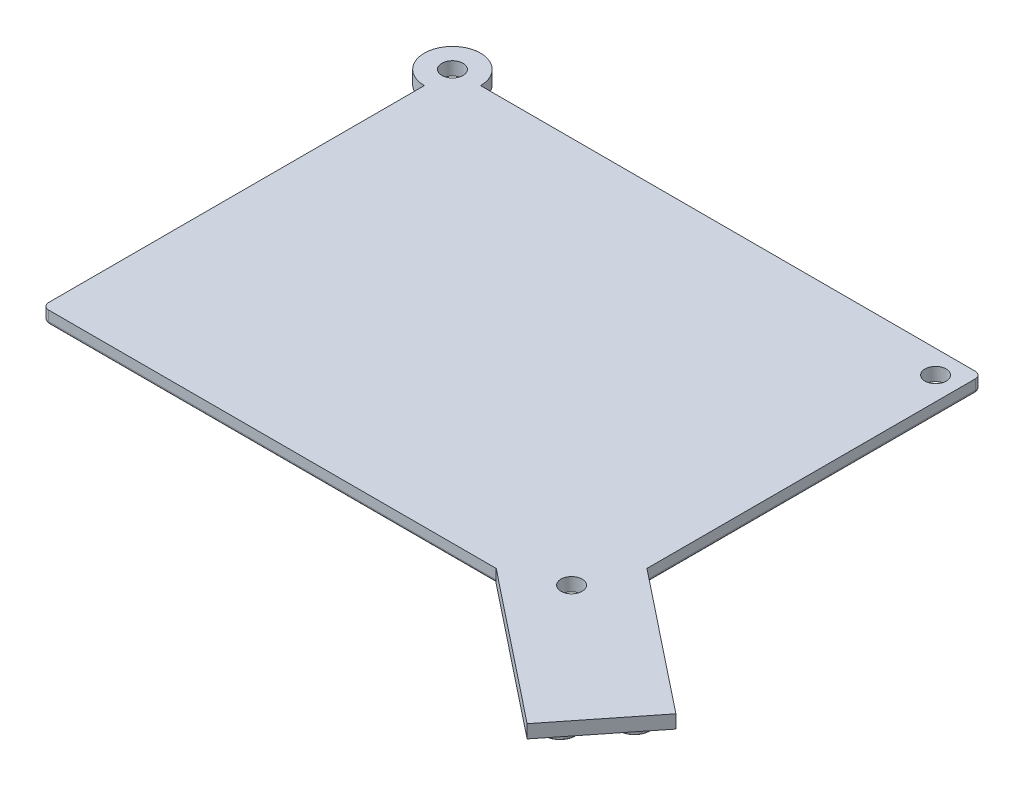
SolidWorks part; units mm, degrees
material "PVC Rigid"
ref_plane "Front Plane" through (0, 0, 0) normal (0, 0, 1) x (1, 0, 0)
ref_plane "Top Plane" through (0, 0, 0) normal (0, 1, 0) x (1, 0, 0)
ref_plane "Right Plane" through (0, 0, 0) normal (1, 0, 0) x (0, 0, -1)
sketch "Sketch1" plane through (0, 0, 0) normal (0, 1, 0) x (1, 0, 0)
  line L0 (40, -31) -> (-40, 31) construction
  line L1 (-40, -31) -> (40, -31)
  line L2 (-40, -31) -> (-40, 26.75)
  line L3 (-35.75, 31) -> (40, 31)
  line L4 (40, -31) -> (40, 31)
  line L5 (-40, -31) -> (40, 31) construction
  arc A5 (-35.75, 31) -> (-40, 26.75) centre (-40, 31) ccw
  point P0 (0, 0)
  point P6 (0, 0)
  point P7 (0, 0)
  dimension "D3" = 4.25
  dimension "D4" = 4.25
  dimension "D5" = 4.25
  dimension "D1" = 80
  dimension "D2" = 62
extrude "Main Body" add sketch "Sketch1" along normal blind 2
fillet "Corners" radius 1 3 edges at (-40, 1, 31) (40, 1, -31) (40, 1, 31)
fillet "Edge" radius 0.5 7 edges at (-39.7071, 0, 30.7071) (39.7071, 0, -30.7071) (39.7071, 0, 30.7071) (-40, 0, 1.625) (1.625, 0, -31) (40, 0, 0) (0, 0, 31)
sketch "Sketch8" plane through (0, 2, 0) normal (0, 1, 0) x (1, 0, 0)
  line L2 (40, -19.6117) -> (61.2107, -36.4473)
  line L3 (40, -30) -> (40, 30) construction
  line L5 (61.2107, -36.4473) -> (51.2636, -48.9794)
  line L6 (51.2636, -48.9794) -> (28.6117, -31)
  line L8 (-39, -31) -> (39, -31) construction
  line L9 (28.6117, -31) -> (40, -19.6117)
  line L10 (39, -30) -> (24.8579, -15.8579) construction
  line L11 (39, -30.5) -> (-39, -30.5) construction
  point P12 (24.4127, -31)
  point P13 (34.3059, -25.3059)
  point P14 (40, -16.911)
  point P15 (28.6117, -31)
  dimension "D1" = 45
  dimension "D2" = 20
  dimension "D3" = 16
  dimension "D4" = 28
extrude "DivingBoard" add sketch "Sketch8" against normal up to surface (2 mm away) up to face at (-0.2552, 0, -0.2552)
sketch "Sketch7" plane through (0, 0, 0) normal (0, -1, 0) x (-1, 0, 0)
  line L0 (39, -31) -> (-28.6117, -31) construction
  line L3 (-40, -19.6117) -> (-40, 30) construction
  line L4 (-39, 31) -> (35.75, 31) construction
  circle A0 centre (40, 31) radius 1.6
  circle A2 centre (-36.5, -27.5) radius 1.6
  circle A3 centre (-36.5, 27.5) radius 1.6
  arc A4 (39.5, 26.7795) -> (35.7795, 30.5) centre (40, 31) ccw construction
  dimension "D1" = 3.2
  dimension "D4" = 3.2
  dimension "D5" = 3.2
  dimension "D2" = 3.5
  dimension "D3" = 3.5
  dimension "D6" = 3.5
extrude "Lid Holes" cut sketch "Sketch7" against normal through all both and the other way through all
sketch "Sketch4" plane through (0, 0, 0) normal (0, -1, 0) x (-1, 0, 0)
  circle A0 centre (-30.0048, 23.7064) radius 2.325
  circle A1 centre (-30.0048, 15.7064) radius 2.325
  point P2 (0, 0)
  dimension "D1" = 4.65
  dimension "D2" = 4.65
  dimension "D3" = 8
extrude "Boss-Extrude3" add sketch "Sketch4" along normal blind 1.6
fillet "Fillet3" radius 0.05 1 edges at (30.0048, -1.6, -26.0314)
pattern_linear "LPattern5" count 4 spacing 8 along (-1, 0, 0) of "Boss-Extrude3", "Fillet3"
sketch "LEGO straightline reference" plane through (0, 0, 0) normal (0, -1, 0) x (-1, 0, 0)
  line L0 (-30.0048, 23.7064) -> (-30.0048, 15.7064) construction
  line L1 (-30.0048, 15.7064) -> (-30.0048, 19.7064) construction
  line L2 (-30.0048, 19.7064) -> (-6.0048, 19.7064) construction
  line L3 (-6.0048, 23.7064) -> (-6.0048, 15.7064) construction
  point P10 (-6.0048, 19.7064)
sketch "Sketch10" plane through (0, 0, 0) normal (0, -1, 0) x (-1, 0, 0)
  line L0 (-56.2371, -42.7133) -> (-31.1728, -22.8191) construction
  line L1 (-61.2107, -36.4473) -> (-51.2636, -48.9794) construction
  line L2 (-55.5909, -37.0935) -> (-50.6173, -43.3596) construction
  circle A0 centre (-55.5909, -37.0935) radius 2.325
  circle A1 centre (-50.6173, -43.3596) radius 2.325
  point P5 (-56.2371, -42.7133)
  point P9 (-53.1041, -40.2266)
  dimension "D2" = 4.65
  dimension "D3" = 4.65
  dimension "D1" = 32
  dimension "D4" = 8
  dimension "D5" = 4
extrude "Pegs (Diagonal)" add sketch "Sketch10" along normal blind 1.6
fillet "Fillet4" radius 0.05 2 edges at (50.6173, -1.6, 41.0346) (55.5909, -1.6, 34.7685)
pattern_linear "LPattern6" count 4 spacing 8 along (-0.7833, 0, -0.6217) of "Fillet4", "Pegs (Diagonal)"
equation "\"D3@Sketch7\"=\"D2@Sketch7\""
equation "\"D4@Sketch7\"=\"D1@Sketch7\""
equation "\"D5@Sketch7\"=\"D1@Sketch7\""
equation "\"D2@Sketch4\"=\"D1@Sketch4\""
equation "\"D3@Sketch10\"=\"D2@Sketch10\""
